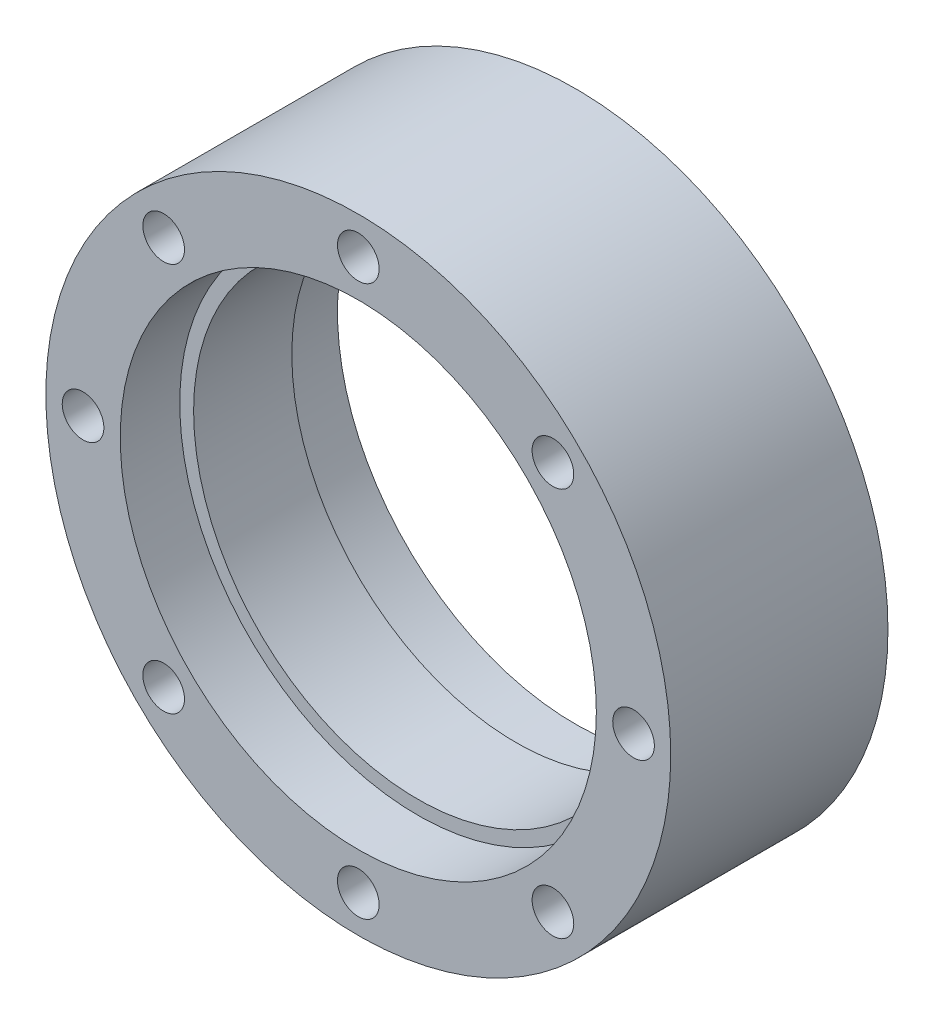
SolidWorks part; units mm, degrees
ref_plane "Front Plane" through (0, 0, 0) normal (0, 0, 1) x (1, 0, 0)
ref_plane "Top Plane" through (0, 0, 0) normal (0, 1, 0) x (1, 0, 0)
ref_plane "Right Plane" through (0, 0, 0) normal (1, 0, 0) x (0, 0, -1)
ref_axis "Z" through (0, 0, 8.03) along (0, 0, -1)
sketch "Sketch7" plane through (0, 0, 0) normal (0, 1, 0) x (1, 0, 0)
  line L0 (16, 7.3) -> (16, 3.3)
  line L2 (16, 3.3) -> (15.07, 3.3)
  line L5 (16, 7.3) -> (21, 7.3)
  line L6 (21, 7.3) -> (21, -7.3)
  line L7 (24.7452, 0) -> (-6.4078, 0) construction
  line L8 (16, -3.3) -> (15.07, -3.3)
  line L9 (16, -7.3) -> (16, -3.3)
  line L10 (15.07, 3.3) -> (15.07, -3.3)
  line L11 (21, -7.3) -> (16, -7.3)
  line L12 (0, -8.03) -> (0, 8.03) construction
  dimension "D2" = 4
  dimension "D4" = 3.3
  dimension "D1" = 15.07
  dimension "D3" = 16
  dimension "D5" = 21
revolve "Revolve1" add sketch "Sketch7" angle 360 about axis through (0, 0, 8.03) along (0, 0, -1)
sketch "Sketch3" plane through (0, 0, 0) normal (0, 0, 1) x (1, 0, 0)
  line L0 (0, 0) -> (0, 18.5) construction
  circle A0 centre (0, 18.5) radius 1.4
  dimension "D1" = 2.8
  dimension "D2" = 18.5
extrude "Cut-Extrude2" cut sketch "Sketch3" against normal through all both and the other way through all
sketch "Sketch4" plane through (0, 0, -7.3) normal (0, 0, -1) x (-1, 0, 0)
  circle A0 centre (0, 18.5) radius 2.35
  circle A1 centre (0, 18.5) radius 1.4 construction
  dimension "D1" = 4.7
extrude "Cut-Extrude4" cut sketch "Sketch4" against normal blind 2.5 and the other way through all
chamfer "Chamfer1" distance 0.1 angle 45 1 edges at (-1.4, 18.5, -4.8)
pattern_circular "CirPattern3" count 4 over 360 about axis through (0, 0, 8.03) along (0, 0, -1) of "Cut-Extrude4"
pattern_circular "CirPattern2" count 8 over 360 about axis through (0, 0, 8.03) along (0, 0, -1) of "Cut-Extrude2"
equation "\"BearingOD\"= 32"
equation "\"BearingHeight\"= 4"
equation "\"SeatsOD\"= \"BearingOD\" + 10"
equation "\"RetainingRingThickness\" = 1.30"
equation "\"BearingBaseDistance\"= 17.2 - 2*\"BearingHeight\"  - \"RetainingRingThickness\"*2"
equation "\"WireHarnessHeight\"= 4"
equation "\"OuterWallWidth\"= 6"
equation "\"OverallOD\" = 42"
equation "\"BearingID\" = 25"
equation "\"OverallHeight\"= \"WireHarnessHeight\" + \"BearingHeight\"*2 + \"BearingBaseDistance\""
equation "\"RetaininRingGrooveDiameter\" = 23.9"
equation "\"ShaftLengthAfterFlange\" = 2*\"BearingHeight\" + \"BearingBaseDistance\" + \"RetainingRingThickness\"*2\t'give a retaining ring thickness of extra clearance"
equation "\"RetainingRingGrooveBase\" = \"ShaftLengthAfterFlange\" - \"RetainingRingThickness\"*2"
equation "\"CoverThickness\" = 1"
equation "\"CoverClearance\" = 1"
equation "\"FlangHeight\" = 3"
equation "\"OuterHousingHeight\" = \"WireHarnessHeight\" + \"BearingHeight\"*2 + \"BearingBaseDistance\""
equation "\"PCBWidth\" = 5"
equation "\"PCBHeight\" = \"OuterHousingHeight\" "
equation "\"PCBThickness\" = 1"
equation "\"NormalDistSidewallPCBToZ\" = (\"OverallOD\"/2) - 1.6\t'radial distance from the z axis to pcb origin on the top/connector side"
equation "\"PCBSidewallCutoutClearance\"= 0.1"
equation "\"D3@Sketch7\"=\"BearingOD\"/2"
equation "\"D4@Sketch7\"=\"BearingBaseDistance\"/2"
equation "\"D5@Sketch7\"=\"OverallOD\"/2"
equation "\"D2@Sketch3\"=(\"OverallOD\"+\"BearingOD\")/4"
equation "\"OutputHubBoltCircleRadius\"= 8"
equation "\"OutputHubOD\"= 27"
equation "\"BearingInnerRaceOD\"= 26.9"
equation "\"StatorWireRadius\"= \"NormalDistSidewallPCBToZ\" - 5.7"
equation "\"MountingHoleRadius\"= (\"OverallOD\"+\"BearingOD\")/4"
